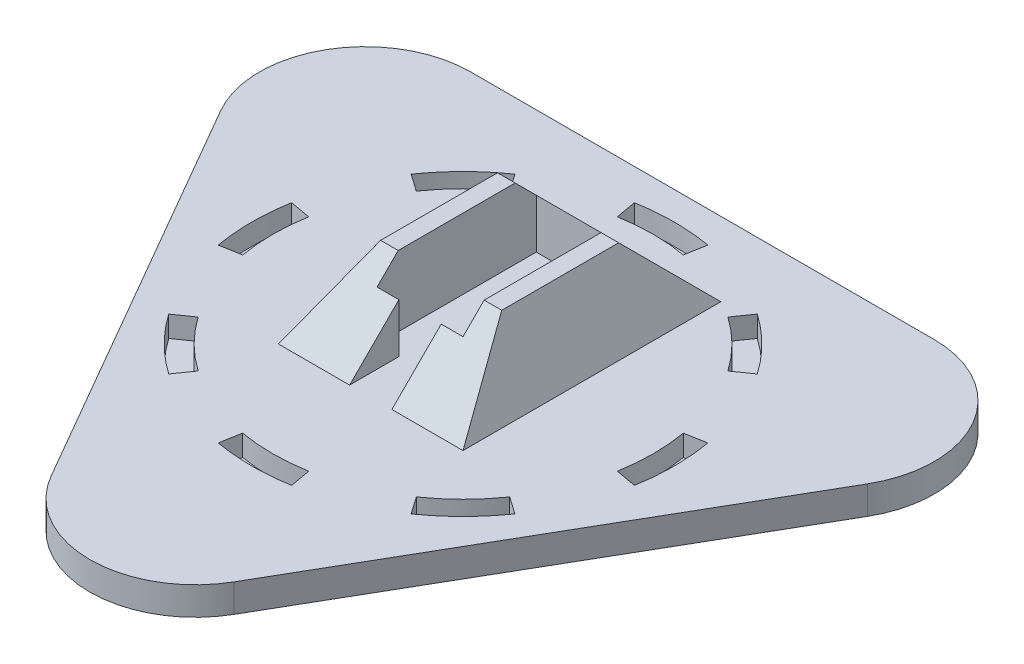
SolidWorks part; units mm, degrees
ref_plane "Front Plane" through (0, 0, 0) normal (0, 0, 1) x (1, 0, 0)
ref_plane "Top Plane" through (0, 0, 0) normal (0, 1, 0) x (1, 0, 0)
ref_plane "Right Plane" through (0, 0, 0) normal (1, 0, 0) x (0, 0, -1)
sketch "Sketch1" plane through (0, 0, 0) normal (0, 1, 0) x (1, 0, 0)
  line L1 (32.909, 34) -> (-32.909, 34)
  line L2 (-45.8993, 11.5) -> (-12.9904, -45.5)
  line L3 (12.9904, -45.5) -> (45.8993, 11.5)
  circle A0 centre (0, 0) radius 27 construction
  circle A1 centre (0, 0) radius 30 construction
  circle A2 centre (0, 0) radius 34 construction
  arc A3 (-45.8993, 11.5) -> (-32.909, 34) centre (-32.909, 19) cw
  arc A4 (32.909, 34) -> (45.8993, 11.5) centre (32.909, 19) cw
  arc A5 (-12.9904, -45.5) -> (12.9904, -45.5) centre (0, -38) ccw
  dimension "D1" = 54
  dimension "D2" = 60
  dimension "D3" = 68
  dimension "D4" = 15
  dimension "D5" = 15
  dimension "D6" = 15
  dimension "D7" = 60
  dimension "D8" = 60
  dimension "D9" = 60
extrude "Boss-Extrude1" add sketch "Sketch1" along normal blind 4
sketch "Sketch2" plane through (0, 4, 0) normal (0, 1, 0) x (1, 0, 0)
  line L0 (4.6885, 26.5898) -> (5.2094, 29.5442)
  line L1 (-4.6885, 26.5898) -> (-5.2094, 29.5442)
  line L2 (0, 0) -> (0, 34) construction
  line L9 (15.4866, 22.1171) -> (17.2073, 24.5746)
  line L10 (22.1171, 15.4866) -> (24.5746, 17.2073)
  line L11 (26.5898, 4.6885) -> (29.5442, 5.2094)
  line L12 (26.5898, -4.6885) -> (29.5442, -5.2094)
  line L13 (22.1171, -15.4866) -> (24.5746, -17.2073)
  line L14 (15.4866, -22.1171) -> (17.2073, -24.5746)
  line L15 (4.6885, -26.5898) -> (5.2094, -29.5442)
  line L16 (-4.6885, -26.5898) -> (-5.2094, -29.5442)
  line L17 (-15.4866, -22.1171) -> (-17.2073, -24.5746)
  line L18 (-22.1171, -15.4866) -> (-24.5746, -17.2073)
  line L19 (-26.5898, -4.6885) -> (-29.5442, -5.2094)
  line L20 (-26.5898, 4.6885) -> (-29.5442, 5.2094)
  line L21 (-22.1171, 15.4866) -> (-24.5746, 17.2073)
  line L22 (-15.4866, 22.1171) -> (-17.2073, 24.5746)
  arc A0 (4.6885, 26.5898) -> (-4.6885, 26.5898) centre (0, 0) ccw
  arc A1 (5.2094, 29.5442) -> (-5.2094, 29.5442) centre (0, 0) ccw
  arc A2 (24.5746, 17.2073) -> (17.2073, 24.5746) centre (0, 0) ccw
  arc A9 (22.1171, 15.4866) -> (15.4866, 22.1171) centre (0, 0) ccw
  arc A10 (29.5442, -5.2094) -> (29.5442, 5.2094) centre (0, 0) ccw
  arc A11 (26.5898, -4.6885) -> (26.5898, 4.6885) centre (0, 0) ccw
  arc A12 (17.2073, -24.5746) -> (24.5746, -17.2073) centre (0, 0) ccw
  arc A13 (15.4866, -22.1171) -> (22.1171, -15.4866) centre (0, 0) ccw
  arc A14 (-5.2094, -29.5442) -> (5.2094, -29.5442) centre (0, 0) ccw
  arc A15 (-4.6885, -26.5898) -> (4.6885, -26.5898) centre (0, 0) ccw
  arc A16 (-24.5746, -17.2073) -> (-17.2073, -24.5746) centre (0, 0) ccw
  arc A17 (-22.1171, -15.4866) -> (-15.4866, -22.1171) centre (0, 0) ccw
  arc A18 (-29.5442, 5.2094) -> (-29.5442, -5.2094) centre (0, 0) ccw
  arc A19 (-26.5898, 4.6885) -> (-26.5898, -4.6885) centre (0, 0) ccw
  arc A20 (-17.2073, 24.5746) -> (-24.5746, 17.2073) centre (0, 0) ccw
  arc A21 (-15.4866, 22.1171) -> (-22.1171, 15.4866) centre (0, 0) ccw
  dimension "D2" = 54
  dimension "D3" = 60
  dimension "D4" = 20
  dimension "D5" = 10
  dimension "D1" = 3
  dimension "D7" = 3
  dimension "D6" = 8
extrude "Cut-Extrude1" cut sketch "Sketch2" against normal blind 3
sketch "Sketch3" plane through (0, 4, 0) normal (0, 1, 0) x (1, 0, 0)
  line L1 (-6.1, -6.1) -> (6.1, -6.1)
  line L2 (-6.1, -6.1) -> (-6.1, 16.5)
  line L3 (-6.1, 16.5) -> (6.1, 16.5)
  line L4 (6.1, -6.1) -> (6.1, 16.5)
  line L5 (-13.1, 23.5) -> (13.1, 23.5)
  line L6 (-13.1, 23.5) -> (-13.1, -13.1)
  line L7 (-13.1, -13.1) -> (13.1, -13.1)
  line L8 (13.1, 23.5) -> (13.1, -13.1)
  point P5 (0, -6.1)
  point P6 (0, 0)
  point P7 (0, 0)
  dimension "D1" = 22.6
  dimension "D2" = 12.2
  dimension "D3" = 6.1
  dimension "D4" = 7
  dimension "D5" = 7
  dimension "D6" = 7
  dimension "D7" = 7
extrude "Boss-Extrude8" add sketch "Sketch3" along normal blind 10
chamfer "Chamfer3" distance 10 distance2 4.5 1 edges at (-13.1, 14, -5.2) first distance on face at (-13.1, 9, -5.2)
chamfer "Chamfer4" distance 10 distance2 4.5 1 edges at (13.1, 14, -5.2) first distance on face at (13.1, 9, -5.2)
chamfer "Chamfer5" distance 10 angle 45 1 edges at (0, 14, -23.5)
chamfer "Chamfer6" distance 10 angle 45 1 edges at (0, 14, 13.1)
sketch "Sketch4" plane through (0, 0, 6.1) normal (0, 0, -1) x (-1, 0, 0)
  line L0 (6.1, 4) -> (-6.1, 4) construction
  line L1 (-3, 4) -> (3, 4)
  line L2 (-3, 4) -> (-3, 11)
  line L3 (-3, 11) -> (3, 11)
  line L4 (3, 4) -> (3, 11)
  line L5 (6.1, 11) -> (-6.1, 11) construction
  point P8 (0, 11)
  dimension "D1" = 6
extrude "Cut-Extrude2" cut sketch "Sketch4" against normal through all
